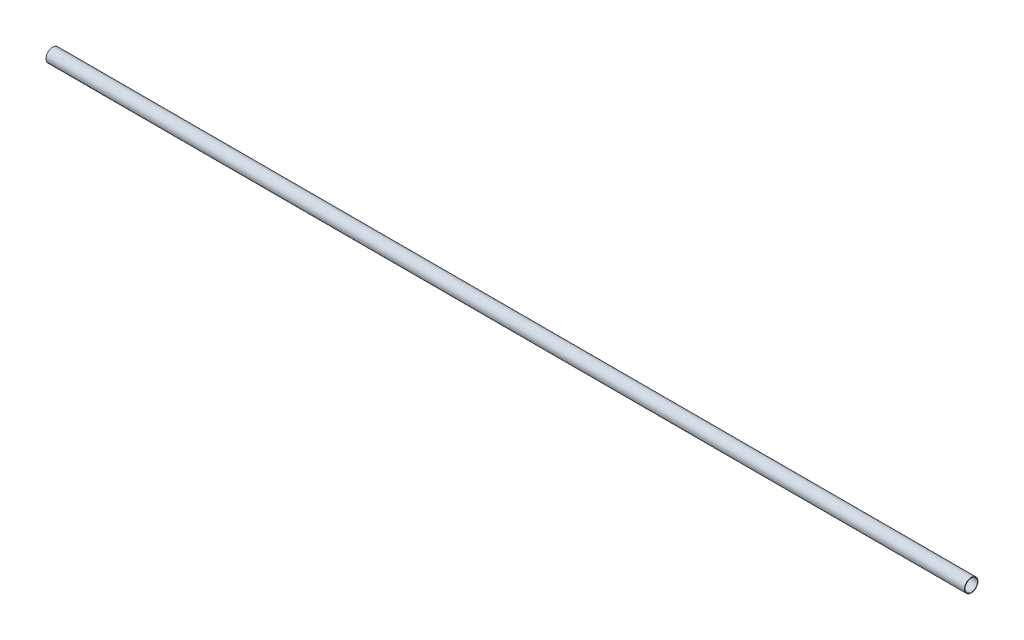
SolidWorks part; units mm, degrees
ref_plane "Front Plane" through (0, 0, 0) normal (0, 0, 1) x (1, 0, 0)
ref_plane "Top Plane" through (0, 0, 0) normal (0, 1, 0) x (1, 0, 0)
ref_plane "Right Plane" through (0, 0, 0) normal (1, 0, 0) x (0, 0, -1)
sketch "Sketch1" plane through (0, 0, 0) normal (1, 0, 0) x (0, 0, -1)
  circle A0 centre (0, 0) radius 12.5
  circle A1 centre (0, 0) radius 11.5
  dimension "D1" = 25
  dimension "D2" = 23
extrude "Boss-Extrude1" add sketch "Sketch1" along normal blind 1700
